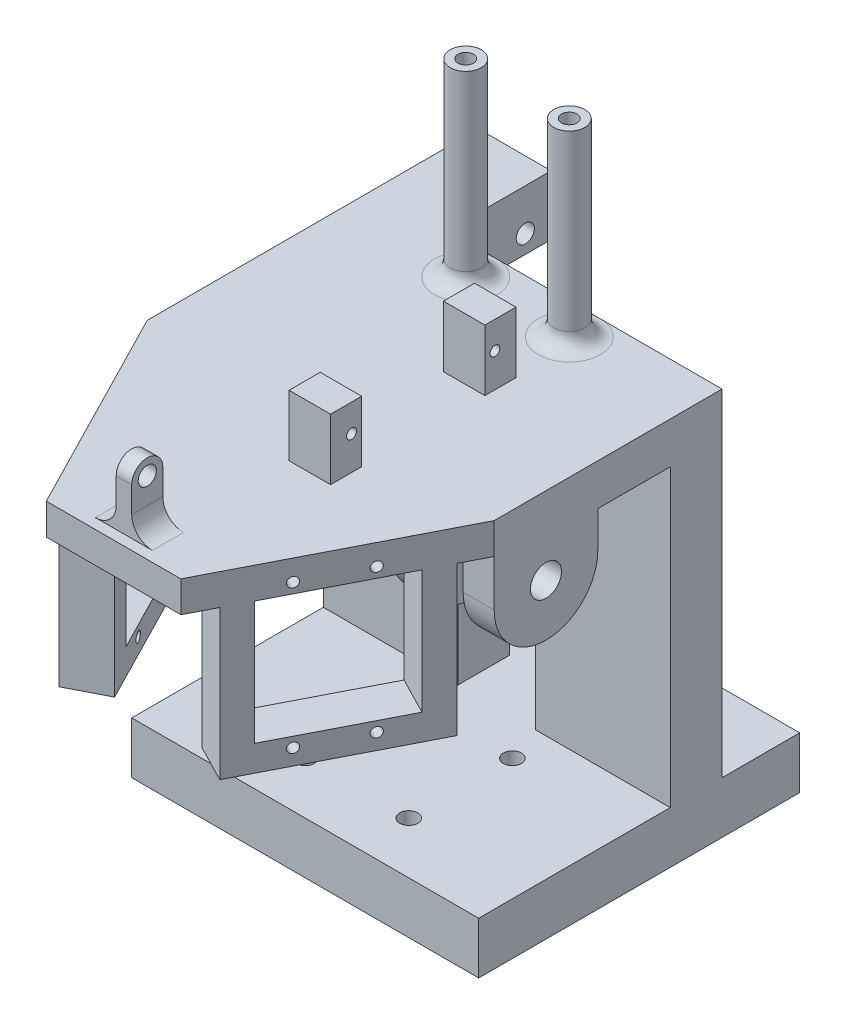
SolidWorks part; units mm, degrees
ref_plane "前视基准面" through (0, 0, 0) normal (0, 0, 1) x (1, 0, 0)
ref_plane "上视基准面" through (0, 0, 0) normal (0, 1, 0) x (1, 0, 0)
ref_plane "右视基准面" through (0, 0, 0) normal (1, 0, 0) x (0, 0, -1)
sketch "草图1" plane through (0, 0, 0) normal (0, 1, 0) x (1, 0, 0)
  line L1 (-33.5, 31) -> (33.5, 31)
  line L2 (-33.5, 31) -> (-33.5, -31)
  line L3 (-33.5, -31) -> (33.5, -31)
  line L4 (33.5, 31) -> (33.5, -31)
  line L5 (-33.5, 31) -> (33.5, -31) construction
  line L6 (-33.5, -31) -> (33.5, 31) construction
  point P0 (0, 0)
  dimension "D1" = 62
  dimension "D2" = 67
extrude "凸台-拉伸1" add sketch "草图1" along normal blind 10
sketch "草图3" plane through (0, 10, 0) normal (0, 1, 0) x (1, 0, 0)
  line L0 (-33.5, 31) -> (-33.5, -31) construction
  line L1 (-33.5, 36) -> (-19.5, 36)
  line L2 (-33.5, 36) -> (-33.5, 16)
  line L3 (-33.5, 16) -> (-19.5, 16)
  line L4 (-19.5, 36) -> (-19.5, 16)
  line L5 (33.5, 31) -> (-33.5, 31) construction
  dimension "D1" = 20
  dimension "D2" = 5
  dimension "D3" = 19.5
extrude "凸台-拉伸2" add sketch "草图3" along normal blind 12.5
sketch "草图4" plane through (-33.5, 0, 0) normal (-1, 0, 0) x (0, 0, 1)
  line L1 (-16, 10) -> (-6, 10)
  line L2 (-16, 10) -> (-16, 75)
  line L3 (-16, 75) -> (-6, 75)
  line L4 (-6, 10) -> (-6, 75)
  dimension "D1" = 10
  dimension "D2" = 65
extrude "凸台-拉伸3" add sketch "草图4" against normal blind 67
sketch "草图5" plane through (0, 75, 0) normal (0, 1, 0) x (1, 0, 0)
  line L0 (33.5, -31) -> (33.5, 6) construction
  line L1 (-33.5, 16) -> (33.5, 16)
  line L2 (-33.5, 16) -> (-33.5, -28)
  line L3 (-33.5, -28) -> (33.5, -28)
  line L4 (33.5, 16) -> (33.5, -28)
  dimension "D1" = 44
extrude "凸台-拉伸4" add sketch "草图5" against normal blind 8
sketch "草图6" plane through (33.5, 0, 0) normal (1, 0, 0) x (0, 0, -1)
  line L0 (6, 10) -> (6, 67) construction
  line L1 (-28, 75) -> (16, 75) construction
  line L2 (-28, 60) -> (-28, 67)
  line L3 (-28, 67) -> (6, 67) construction
  line L5 (-28, 67) -> (-8, 67)
  line L6 (-8, 67) -> (-8, 60)
  arc A0 (-28, 60) -> (-8, 60) centre (-18, 60) ccw
  dimension "D1" = 24
  dimension "D2" = 15
  dimension "D3" = 20
extrude "凸台-拉伸5" add sketch "草图6" against normal blind 20
sketch "草图7" plane through (33.5, 0, 0) normal (1, 0, 0) x (0, 0, -1)
  line L0 (-28, 60) -> (-28, 70.0002)
  line L1 (-28, 60) -> (-28, 75) construction
  line L2 (-28, 70.0002) -> (-8, 70.0002)
  line L3 (-8, 70.0002) -> (-8, 60)
  arc A0 (-28, 60) -> (-8, 60) centre (-18, 60) ccw construction
  arc A1 (-28, 60) -> (-8, 60) centre (-18, 60) ccw
extrude "切除-拉伸1" cut sketch "草图7" against normal blind 8 from offset 6 offset against normal yes
sketch "草图8" plane through (0, 75, 0) normal (0, 1, 0) x (1, 0, 0)
  line L0 (0, -68) -> (13, -68)
  line L2 (13, -68) -> (33.5, -28)
  line L3 (33.5, -28) -> (0, -28)
  line L4 (0, -28) -> (0, -68)
  line L5 (-33.5, -28) -> (33.5, -28) construction
  line L6 (33.5, -31) -> (33.5, 6) construction
  dimension "D1" = 13
  dimension "D2" = 40
extrude "凸台-拉伸6" add sketch "草图8" against normal blind 6
sketch "草图9" plane through (33.5, 0, 0) normal (1, 0, 0) x (0, 0, -1)
  circle A0 centre (-18, 60) radius 3
  dimension "D1" = 6
extrude "切除-拉伸2" cut sketch "草图9" against normal blind 23
sketch "草图10" plane through (37.8963, 0, 19.4219) normal (0.8899, 0, 0.4561) x (0.4561, 0, -0.8899)
  line L1 (-44, 75) -> (-15, 75)
  line L4 (-15, 75) -> (-15, 40.2)
  line L5 (-15, 40.2) -> (-43, 40.2)
  line L9 (-44, 45.2) -> (-20, 45.2)
  line L10 (-20, 45.2) -> (-20, 69)
  line L11 (-20, 69) -> (-44, 69)
  line L12 (-54.5863, 75) -> (-9.6391, 75) construction
  line L14 (-44, 75) -> (-49, 75)
  line L15 (-54.5863, 75) -> (-9.6391, 75) construction
  line L16 (-44, 69) -> (-44, 45.2)
  line L17 (-43, 40.2) -> (-49, 40.2)
  line L18 (-49, 75) -> (-49, 40.2)
  dimension "D1" = 5
  dimension "D2" = 5
  dimension "D3" = 29
  dimension "D4" = 15
  dimension "D5" = 24
  dimension "D6" = 28
  dimension "D7" = 5
  dimension "D8" = 6
  dimension "D9" = 23.8
extrude "凸台-拉伸7" add sketch "草图10" against normal blind 8
sketch "草图12" plane through (0, 75, 0) normal (0, 1, 0) x (1, 0, 0)
  line L1 (-33.5, 36) -> (-19.5, 36)
  line L2 (-33.5, 36) -> (-33.5, 16)
  line L3 (-33.5, 16) -> (-19.5, 16)
  line L4 (-19.5, 36) -> (-19.5, 16)
extrude "凸台-拉伸8" add sketch "草图12" against normal blind 11.5
sketch "草图13" plane through (30.7768, 0, 15.7731) normal (-0.8899, 0, -0.4561) x (-0.4561, 0, 0.8899)
  line L0 (54.5863, 69) -> (49, 69) construction
  line L7 (20, 69) -> (20, 45.2) construction
  line L8 (20, 45.2) -> (44, 45.2) construction
  circle A0 centre (38.5, 70.95) radius 0.95
  circle A1 centre (26.5, 70.95) radius 0.95
  circle A2 centre (26.5, 43.25) radius 0.95
  circle A3 centre (38.5, 43.25) radius 0.95
  dimension "D2" = 6.5
  dimension "D3" = 1.95
  dimension "D4" = 1.95
  dimension "D5" = 12
  dimension "D6" = 1.9
  dimension "D7" = 1.9
  dimension "D13" = 1.9
  dimension "D14" = 1.9
extrude "切除-拉伸4" cut sketch "草图13" against normal up to surface (8 mm away) up to face at (23.2757, 63.3, 47.9499)
sketch "草图14" plane through (0, 75, 0) normal (0, 1, 0) x (1, 0, 0)
  line L0 (33.5, 6) -> (-33.5, 6) construction
  line L1 (3.7, -2) -> (11.7, -2)
  line L2 (3.7, -2) -> (3.7, -8)
  line L3 (3.7, -8) -> (11.7, -8)
  line L4 (11.7, -2) -> (11.7, -8)
  line L5 (11.7, -31.8) -> (11.7, -37.8)
  line L6 (3.7, -37.8) -> (11.7, -37.8)
  line L7 (3.7, -31.8) -> (3.7, -37.8)
  line L8 (3.7, -31.8) -> (11.7, -31.8)
  dimension "D1" = 11.7
  dimension "D2" = 3.7
  dimension "D3" = 6
  dimension "D4" = 14
  dimension "D5" = 6
  dimension "D6" = 8
  dimension "D7" = 23.8
extrude "凸台-拉伸9" add sketch "草图14" along normal blind 11.8
sketch "草图15" plane through (3.7, 0, 0) normal (-1, 0, 0) x (0, 0, 1)
  line L0 (8, 86.8) -> (8, 75) construction
  line L1 (28, 75) -> (-36, 75) construction
  line L2 (31.8, 75) -> (37.8, 75) construction
  line L3 (31.8, 86.8) -> (31.8, 75) construction
  circle A0 centre (33.75, 81.5) radius 0.95
  circle A1 centre (6.05, 81.5) radius 0.95
  dimension "D1" = 1.95
  dimension "D2" = 1.95
  dimension "D3" = 1.9
  dimension "D4" = 1.9
  dimension "D5" = 6.5
  dimension "D6" = 6.5
extrude "切除-拉伸5" cut sketch "草图15" against normal blind 11.8
sketch "草图16" plane through (0, 75, 0) normal (0, 1, 0) x (1, 0, 0)
  line L1 (-1.5, -60) -> (1.5, -60)
  line L2 (-1.5, -60) -> (-1.5, -66)
  line L3 (-1.5, -66) -> (1.5, -66)
  line L4 (1.5, -60) -> (1.5, -66)
  point P4 (0, -66)
  dimension "D2" = 6
  dimension "D3" = 3
  dimension "D4" = 60
extrude "凸台-拉伸10" add sketch "草图16" along normal blind 12
fillet "圆角1" 2 edges at (0, 87, 66) (0, 87, 60) type full round first side face at (0, 79.8, 66) second side face at (0, 79.8, 60) middle face at (0, 87, 63)
sketch "草图17" plane through (-1.5, 0, 0) normal (-1, 0, 0) x (0, 0, 1)
  circle A0 centre (63, 84) radius 1.75
  arc A1 (66, 84) -> (60, 84) centre (63, 84) ccw construction
  dimension "D1" = 3.5
extrude "切除-拉伸6" cut sketch "草图17" against normal blind 7
sketch "草图18" plane through (0, 75, 0) normal (0, 1, 0) x (1, 0, 0)
  line L0 (33.5, 16) -> (-19.5, 16) construction
  circle A0 centre (10, 10) radius 3
  dimension "D1" = 6
  dimension "D2" = 6
  dimension "D3" = 10
extrude "凸台-拉伸11" add sketch "草图18" along normal blind 36.5
fillet "圆角2" radius 3 1 edges at (10, 75, -7)
mirror "镜向1" about plane through (0, 0, 0) normal (1, 0, 0) of "圆角2", "凸台-拉伸11", "切除-拉伸4", "凸台-拉伸7", "切除-拉伸2", "凸台-拉伸6", "切除-拉伸1", "凸台-拉伸5"
sketch "草图20" plane through (-33.5, 0, 0) normal (-1, 0, 0) x (0, 0, 1)
  line L0 (-36, 63.5) -> (-16, 63.5) construction
  line L1 (-36, 63.5) -> (-36, 75) construction
  circle A0 centre (-31, 67) radius 1.75
  circle A1 centre (-21, 67) radius 1.75
  circle A2 centre (-31, 19) radius 1.75
  circle A3 centre (-21, 19) radius 1.75
  dimension "D1" = 3.5
  dimension "D2" = 10
  dimension "D3" = 48
  dimension "D4" = 3.5
  dimension "D5" = 5
extrude "切除-拉伸7" cut sketch "草图20" against normal blind 35
sketch "草图21" plane through (0, 0, -16) normal (0, 0, -1) x (-1, 0, 0)
  line L1 (-7.5, 65) -> (7.5, 65)
  line L2 (-7.5, 65) -> (-7.5, 10)
  line L3 (-7.5, 10) -> (7.5, 10)
  line L4 (7.5, 65) -> (7.5, 10)
  line L5 (-33.5, 10) -> (19.5, 10) construction
  point P8 (0, 10)
  dimension "D1" = 15
  dimension "D2" = 55
extrude "切除-拉伸8" cut sketch "草图21" against normal blind 35
sketch "草图24" plane through (0, 10, 0) normal (0, 1, 0) x (1, 0, 0)
  line L0 (-33.5, -31) -> (33.5, -31) construction
  circle A0 centre (-10, -21) radius 1.75
  circle A1 centre (10, -21) radius 1.75
  circle A2 centre (-10, -1) radius 1.75
  circle A3 centre (10, -1) radius 1.75
  point P10 (0, -31)
  dimension "D1" = 20
  dimension "D2" = 20
  dimension "D5" = 10
  dimension "D6" = 3.5
  dimension "D7" = 10
  dimension "D3" = 20
  dimension "D4" = 20
extrude "切除-拉伸11" cut sketch "草图24" against normal blind 18
sketch "草图25" plane through (0, 111.5, 0) normal (0, 1, 0) x (1, 0, 0)
  circle A0 centre (10, 10) radius 1.5
  circle A1 centre (-10, 10) radius 1.5
  dimension "D1" = 3
  dimension "D2" = 3
extrude "切除-拉伸12" cut sketch "草图25" against normal blind 10
fillet "圆角3" radius 4 2 edges at (-1.5, 75, 63) (1.5, 75, 63)
sketch "草图26" plane through (0, 69, 0) normal (0, -1, 0) x (1, 0, 0)
  line L0 (-13, 68) -> (13, 68) construction
  line L1 (-5.1, 63.88) -> (5.2, 63.88)
  line L2 (-5.1, 63.88) -> (-5.1, 60.08)
  line L3 (-5.1, 60.08) -> (5.2, 60.08)
  line L4 (5.2, 63.88) -> (5.2, 60.08)
  line L5 (-5.1, 63.88) -> (5.2, 60.08) construction
  line L6 (-5.1, 60.08) -> (5.2, 63.88) construction
  line L7 (-33.5, -31) -> (-33.5, 31) construction
  point P0 (0.05, 61.98)
  dimension "D1" = 3.8
  dimension "D2" = 10.3
  dimension "D3" = 4.12
  dimension "D4" = 28.4
extrude "凸台-拉伸12" add sketch "草图26" along normal blind 1
sketch "草图27" plane through (0, 68, 0) normal (0, -1, 0) x (1, 0, 0)
  line L0 (-13, 68) -> (13, 68) construction
  line L4 (-33.5, -31) -> (-33.5, 31) construction
  circle A0 centre (0.05, 62) radius 1.4
  dimension "D1" = 2.8
  dimension "D2" = 6
  dimension "D3" = 33.55
extrude "切除-拉伸13" cut sketch "草图27" against normal blind 4
